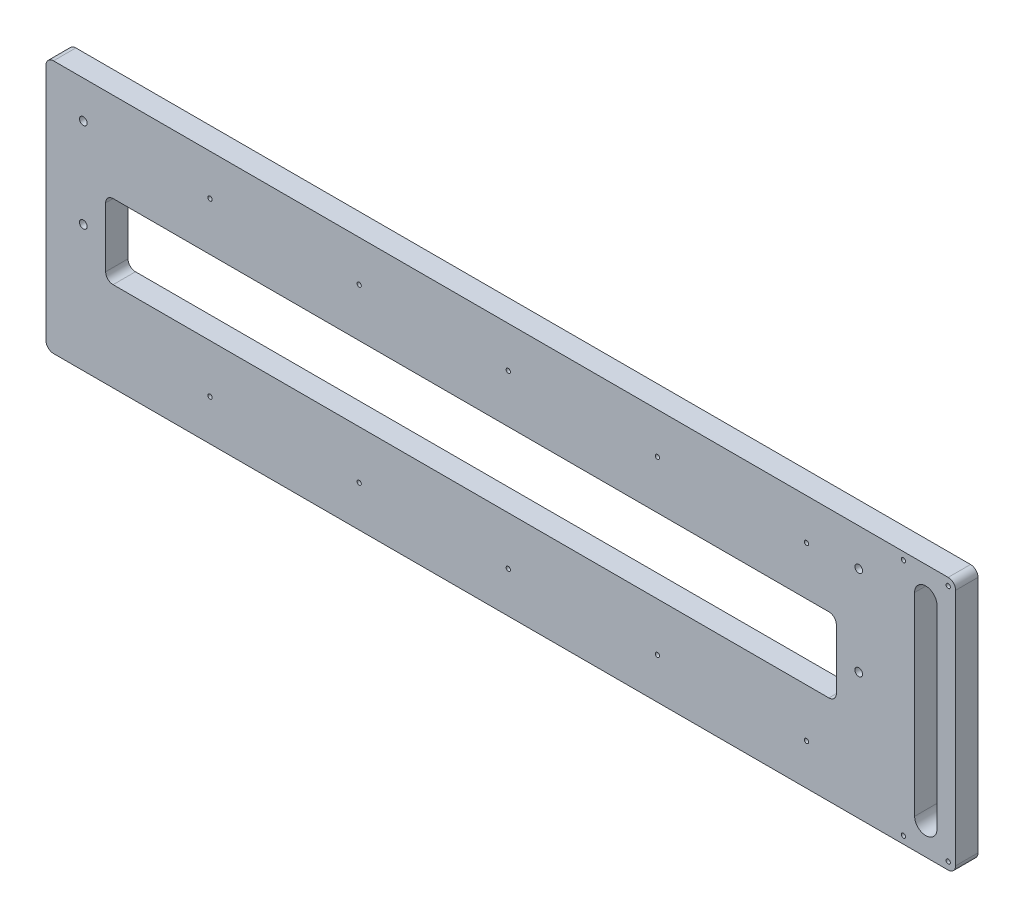
SolidWorks part; units mm, degrees
ref_plane "Front Plane" through (0, 0, 0) normal (0, 0, 1) x (1, 0, 0)
ref_plane "Top Plane" through (0, 0, 0) normal (0, 1, 0) x (1, 0, 0)
ref_plane "Right Plane" through (0, 0, 0) normal (1, 0, 0) x (0, 0, -1)
sketch "Sketch2" plane through (0, 0, 0) normal (0, 0, 1) x (1, 0, 0)
  line L0 (330.2, 107.95) -> (330.2, -107.95)
  line L1 (-393.7, -107.95) -> (330.2, -107.95)
  line L2 (-393.7, -107.95) -> (-393.7, 107.95)
  line L3 (-393.7, 107.95) -> (330.2, 107.95)
  line L5 (-393.7, -107.95) -> (393.7, 107.95) construction
  line L6 (-393.7, 107.95) -> (393.7, -107.95) construction
  point P0 (0, 0)
  dimension "D1" = 787.4
  dimension "D2" = 215.9
extrude "Boss-Extrude1" add sketch "Sketch2" along normal blind 19.05
sketch "Sketch13" plane through (0, 0, 19.05) normal (0, 0, 1) x (1, 0, 0)
  line L1 (-336.55, -31.75) -> (273.05, -31.75)
  line L2 (-342.9, -25.4) -> (-342.9, 25.4)
  line L3 (-336.55, 31.75) -> (273.05, 31.75)
  line L4 (279.4, -25.4) -> (279.4, 25.4)
  line L5 (-342.9, -31.75) -> (279.4, 31.75) construction
  line L6 (-342.9, 31.75) -> (279.4, -31.75) construction
  line L7 (-393.7, 107.95) -> (-393.7, -107.95) construction
  line L9 (330.2, -107.95) -> (330.2, 107.95) construction
  arc A0 (273.05, 31.75) -> (279.4, 25.4) centre (273.05, 25.4) cw
  arc A1 (273.05, -31.75) -> (279.4, -25.4) centre (273.05, -25.4) ccw
  arc A2 (-336.55, -31.75) -> (-342.9, -25.4) centre (-336.55, -25.4) cw
  arc A3 (-342.9, 25.4) -> (-336.55, 31.75) centre (-336.55, 25.4) cw
  point P19 (279.4, 0)
  dimension "D3" = 6.35
  dimension "D1" = 63.5
  dimension "D2" = 50.8
  dimension "D4" = 50.8
extrude "Cut-Extrude3" cut sketch "Sketch13" against normal through all
hole_wizard "#27 (0.144) Diameter Hole1" positions "Sketch14" profile "Sketch15" hole size "#27" standard "ANSI Inch" end condition through all
sketch "Sketch14" plane through (0, 0, 0) normal (0, 0, -1) x (-1, 0, 0)
  line L1 (-254, -73.025) -> (254, -73.025) construction
  line L2 (-254, -73.025) -> (-254, 73.025) construction
  line L3 (-254, 73.025) -> (254, 73.025) construction
  line L4 (254, -73.025) -> (254, 73.025) construction
  line L5 (-254, -73.025) -> (254, 73.025) construction
  line L6 (-254, 73.025) -> (254, -73.025) construction
  point P1 (0, 0)
  point P22 (-254, 73.025)
  point P36 (-127, 73.025)
  point P37 (0, 73.025)
  point P38 (127, 73.025)
  point P39 (254, 73.025)
  point P40 (-127, -73.025)
  point P41 (0, -73.025)
  point P42 (127, -73.025)
  point P43 (254, -73.025)
  point P44 (-254, -73.025)
  dimension "D1" = 146.05
  dimension "D2" = 508
  dimension "D3" = 5
  dimension "D4" = 2
sketch "Sketch15" plane through (0, 0, 0) normal (1, 0, 0) x (0, 1, 0)
  line L0 (0, 0) -> (0, 19.05)
  line L1 (0, 19.05) -> (1.8288, 19.05)
  line L2 (1.8288, 19.05) -> (1.8288, 0)
  line L5 (1.8288, 0) -> (0, 0)
  line L11 (0, -6.35) -> (0, 107.95) construction
  dimension "Thru Hole Dia." = 3.6576
  dimension "Thru Hole Depth" = 19.05
hole_wizard "1/4 Clearance Hole1" positions "Sketch18" profile "Sketch19" hole size "1/4" standard "ANSI Inch" end condition through all
sketch "Sketch18" plane through (0, 0, 0) normal (0, 0, -1) x (-1, 0, 0)
  line L0 (-330.2, -107.95) -> (-330.2, 107.95) construction
  line L1 (-330.2, 107.95) -> (393.7, 107.95) construction
  line L2 (393.7, 107.95) -> (393.7, -107.95) construction
  line L5 (-298.45, 76.2) -> (361.95, 76.2) construction
  line L6 (-298.45, 76.2) -> (-298.45, 0) construction
  line L7 (-298.45, 0) -> (361.95, 0) construction
  line L8 (361.95, 76.2) -> (361.95, 0) construction
  point P0 (-298.45, 76.2)
  point P2 (361.95, 76.2)
  point P73 (361.95, 0)
  point P128 (-298.45, 0)
  dimension "D1" = 31.75
  dimension "D2" = 31.75
  dimension "D3" = 31.75
  dimension "D4" = 31.75
  dimension "D5" = 76.2
sketch "Sketch19" plane through (298.45, 76.2, 0) normal (1, 0, 0) x (0, 1, 0)
  line L0 (0, 0) -> (0, 19.05)
  line L1 (0, 19.05) -> (3.2639, 19.05)
  line L2 (3.2639, 19.05) -> (3.2639, 0)
  line L5 (3.2639, 0) -> (0, 0)
  line L11 (0, -6.35) -> (0, 107.95) construction
  dimension "Thru Hole Dia." = 6.5278
  dimension "Thru Hole Depth" = 19.05
sketch "Sketch22" plane through (330.2, 0, 0) normal (1, 0, 0) x (0, 0, -1)
  line L1 (-19.05, 107.95) -> (0, 107.95)
  line L2 (-19.05, 107.95) -> (-19.05, -107.95)
  line L3 (-19.05, -107.95) -> (0, -107.95)
  line L4 (0, 107.95) -> (0, -107.95)
extrude "Boss-Extrude2" add sketch "Sketch22" along normal blind 50.8
fillet "Fillet1" radius 6.35 4 edges at (381, 107.95, 9.525) (381, -107.95, 9.525) (-393.7, -107.95, 9.525) (-393.7, 107.95, 9.525)
hole_wizard "#6 Clearance Hole1" positions "Sketch23" profile "Sketch24" hole size "#6" standard "ANSI Inch" end condition through all
sketch "Sketch23" plane through (0, 0, 19.05) normal (0, 0, 1) x (1, 0, 0)
  line L0 (355.6, 107.95) -> (355.6, -107.95) construction
  line L1 (374.65, 107.95) -> (-387.35, 107.95) construction
  line L2 (-387.35, -107.95) -> (374.65, -107.95) construction
  line L4 (381, 101.6) -> (381, -101.6) construction
  line L6 (374.65, -101.6) -> (336.55, -101.6) construction
  line L7 (374.65, -101.6) -> (374.65, 101.6) construction
  line L8 (374.65, 101.6) -> (336.55, 101.6) construction
  line L9 (336.55, -101.6) -> (336.55, 101.6) construction
  line L10 (374.65, -101.6) -> (336.55, 101.6) construction
  line L11 (374.65, 101.6) -> (336.55, -101.6) construction
  point P9 (355.6, 0)
  point P10 (336.55, 101.6)
  point P55 (374.65, -101.6)
  point P56 (374.65, 101.6)
  point P57 (336.55, -101.6)
  dimension "D1" = 25.4
  dimension "D2" = 203.2
  dimension "D3" = 38.1
sketch "Sketch24" plane through (336.55, -101.6, 19.05) normal (1, 0, 0) x (0, -1, 0)
  line L0 (0, 0) -> (0, 19.05)
  line L1 (0, 19.05) -> (1.8288, 19.05)
  line L2 (1.8288, 19.05) -> (1.8288, 0)
  line L5 (1.8288, 0) -> (0, 0)
  line L11 (0, -6.35) -> (0, 107.95) construction
  dimension "Thru Hole Dia." = 3.6576
  dimension "Thru Hole Depth" = 19.05
sketch "Sketch25" plane through (0, 0, 19.05) normal (0, 0, 1) x (1, 0, 0)
  line L0 (336.55, 101.6) -> (374.65, -101.6) construction
  line L1 (355.6, -82.55) -> (355.6, 82.55) construction
  line L2 (346.075, -82.55) -> (346.075, 82.55)
  line L3 (365.125, -82.55) -> (365.125, 82.55)
  arc A0 (346.075, -82.55) -> (365.125, -82.55) centre (355.6, -82.55) ccw
  arc A1 (365.125, 82.55) -> (346.075, 82.55) centre (355.6, 82.55) ccw
  point P6 (355.6, 0)
  dimension "D1" = 19.05
  dimension "D2" = 165.1
extrude "Cut-Extrude4" cut sketch "Sketch25" against normal blind 76.2
